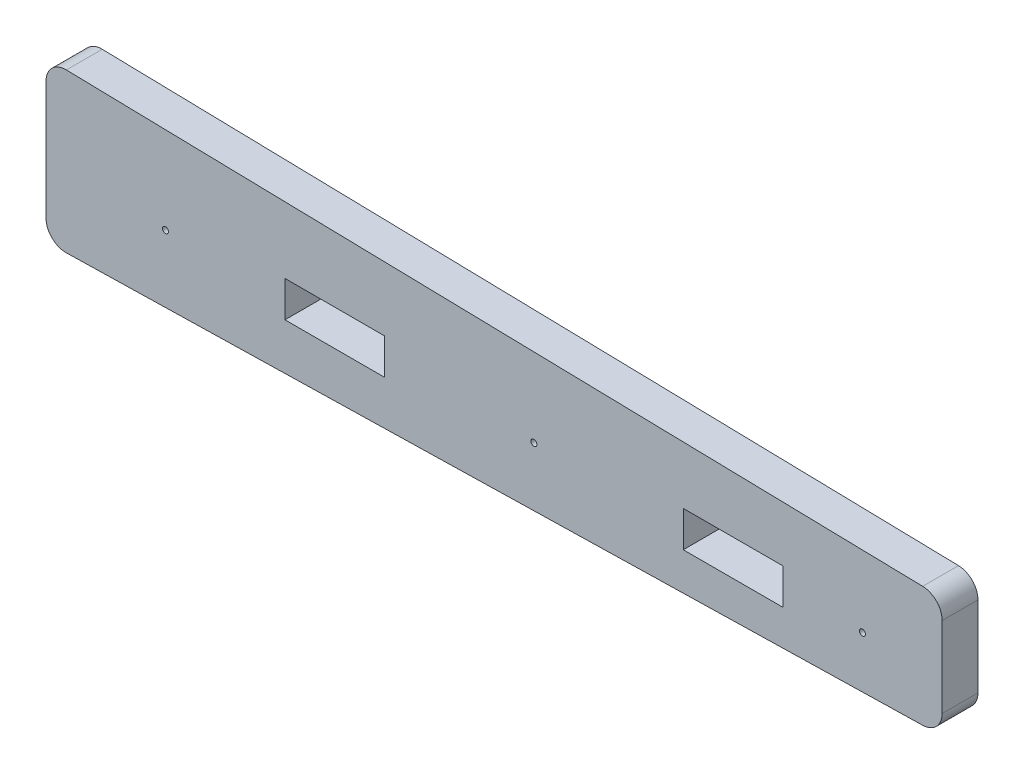
SolidWorks part; units mm, degrees
material "Teak"
ref_plane "Front Plane" through (0, 0, 0) normal (0, 0, 1) x (1, 0, 0)
ref_plane "Top Plane" through (0, 0, 0) normal (0, 1, 0) x (1, 0, 0)
ref_plane "Right Plane" through (0, 0, 0) normal (1, 0, 0) x (0, 0, -1)
sketch "Sketch1" plane through (0, 0, 0) normal (0, 0, 1) x (1, 0, 0)
  line L0 (-225, 40) -> (-225, -40)
  line L5 (-225, -40) -> (225, -30)
  line L6 (225, -30) -> (225, 30)
  line L7 (-105, 4) -> (-55, 4)
  line L8 (-105, 4) -> (-105, -14)
  line L9 (-105, -14) -> (-55, -14)
  line L10 (-55, 4) -> (-55, -14)
  line L11 (-105, 4) -> (-55, -14) construction
  line L12 (-105, -14) -> (-55, 4) construction
  line L13 (95, 4) -> (145, 4)
  line L14 (95, 4) -> (95, -14)
  line L15 (95, -14) -> (145, -14)
  line L16 (145, 4) -> (145, -14)
  line L17 (95, 4) -> (145, -14) construction
  line L18 (95, -14) -> (145, 4) construction
  line L19 (225, 30) -> (-225, 40)
  point P0 (0, 0)
  point P4 (-225, 0)
  point P11 (120, -5)
  point P17 (225, 0)
  point P22 (0, 35)
  point P26 (-80, -5)
  dimension "D1" = 50
  dimension "D2" = 18
  dimension "D3" = 60
  dimension "D4" = 80
  dimension "D5" = 450
  dimension "D6" = 150
  dimension "D7" = 80
  dimension "D8" = 5
extrude "Основа" add sketch "Sketch1" along normal blind 18
fillet "Fillet1" radius 10 4 edges at (-225, -40, 9) (-225, 40, 9) (225, -30, 9) (225, 30, 9)
sketch "Sketch2" plane through (0, 0, 18) normal (0, 0, 1) x (1, 0, 0)
  line L0 (-55, -14) -> (-55, 4) construction
  line L1 (145, -5) -> (225, -5) construction
  line L2 (145, -14) -> (145, 4) construction
  line L3 (225, -20.2198) -> (225, 20.2198) construction
  line L4 (95, -5) -> (-55, -5) construction
  line L5 (95, 4) -> (95, -14) construction
  line L6 (-105, -5) -> (-225, -5) construction
  line L7 (-105, 4) -> (-105, -14) construction
  line L8 (-225, 29.7753) -> (-225, -29.7753) construction
  circle A0 centre (-165, -5) radius 1.5
  circle A1 centre (20, -5) radius 1.5
  circle A2 centre (185, -5) radius 1.5
  point P9 (-55, -5)
  point P25 (185, -5)
  point P26 (20, -5)
  point P27 (0, 0)
  point P28 (-165, -5)
  dimension "D1" = 3
extrude "Под шурупы" cut sketch "Sketch2" against normal up to next
